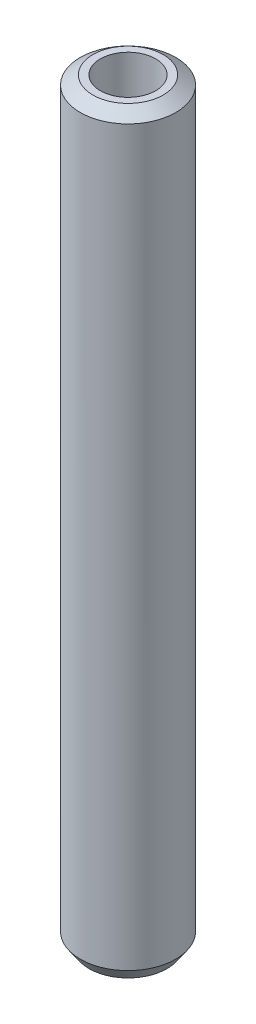
SolidWorks part; units mm, degrees
ref_plane "Front Plane" through (0, 0, 0) normal (0, 0, 1) x (1, 0, 0)
ref_plane "Top Plane" through (0, 0, 0) normal (0, 1, 0) x (1, 0, 0)
ref_plane "Right Plane" through (0, 0, 0) normal (1, 0, 0) x (0, 0, -1)
sketch "Sketch1" plane through (0, 0, 0) normal (0, 1, 0) x (1, 0, 0)
  circle A0 centre (0, 0) radius 12.5
  dimension "SHAFT_OD" = 25
extrude "Boss-Extrude1" add sketch "Sketch1" along normal blind 197.476
sketch "Sketch2" plane through (0, 0, 0) normal (0, 1, 0) x (1, 0, 0)
  circle A0 centre (0, 0) radius 7.2389
  dimension "BORE_D" = 14.4779
extrude "Cut-Extrude1" cut sketch "Sketch2" along normal through all
chamfer "Chamfer1" distance 2.3064 angle 55.142 2 edges at (0, 197.476, 12.5) (0, 0, 12.5) first distance on face at (0, 197.476, 12.5) first distance on face at (0, 0, 7.2389)
